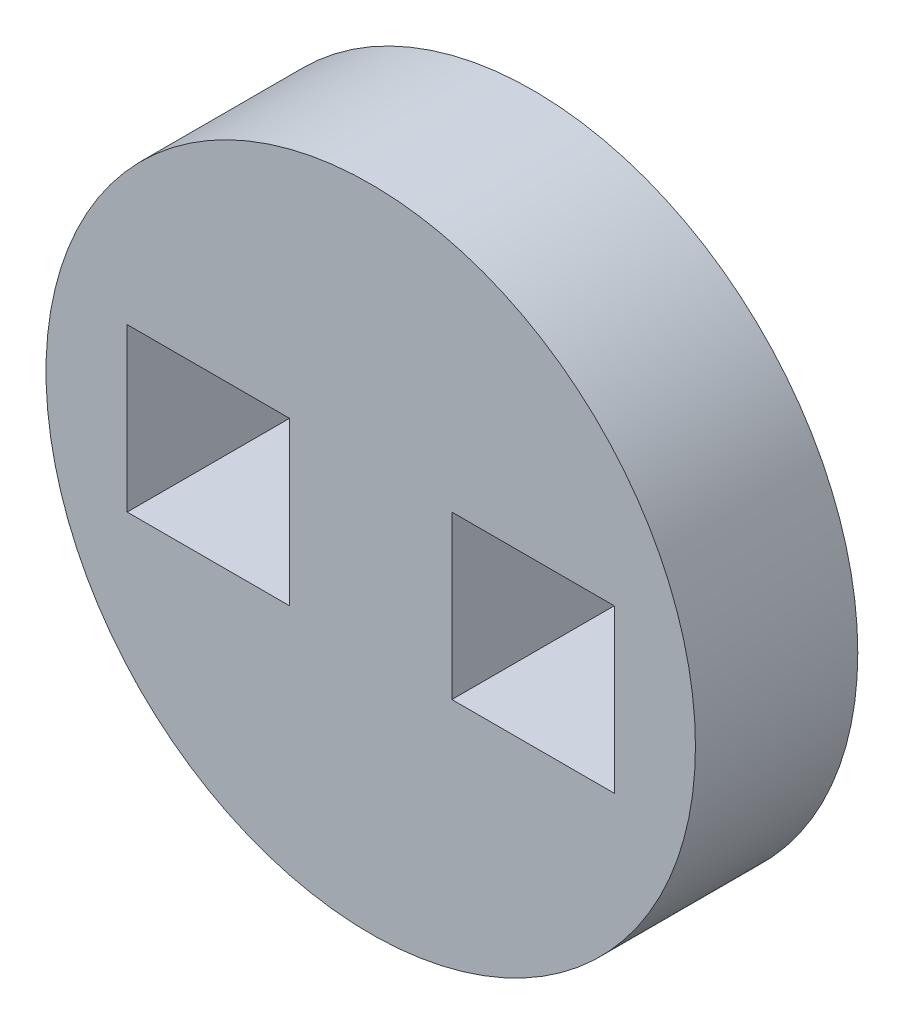
SolidWorks part; units mm, degrees
ref_plane "Front Plane" through (0, 0, 0) normal (0, 0, 1) x (1, 0, 0)
ref_plane "Top Plane" through (0, 0, 0) normal (0, 1, 0) x (1, 0, 0)
ref_plane "Right Plane" through (0, 0, 0) normal (1, 0, 0) x (0, 0, -1)
sketch "Sketch1" plane through (0, 0, 0) normal (0, 0, 1) x (1, 0, 0)
  line L1 (1.5875, -1.5875) -> (4.7625, -1.5875)
  line L2 (1.5875, -1.5875) -> (1.5875, 1.5875)
  line L3 (1.5875, 1.5875) -> (4.7625, 1.5875)
  line L4 (4.7625, -1.5875) -> (4.7625, 1.5875)
  line L5 (1.5875, -1.5875) -> (4.7625, 1.5875) construction
  line L6 (1.5875, 1.5875) -> (4.7625, -1.5875) construction
  line L7 (-4.7625, -1.5875) -> (-1.5875, -1.5875)
  line L8 (-4.7625, -1.5875) -> (-4.7625, 1.5875)
  line L9 (-4.7625, 1.5875) -> (-1.5875, 1.5875)
  line L10 (-1.5875, -1.5875) -> (-1.5875, 1.5875)
  line L11 (-4.7625, -1.5875) -> (-1.5875, 1.5875) construction
  line L12 (-4.7625, 1.5875) -> (-1.5875, -1.5875) construction
  circle A0 centre (0, 0) radius 6.35
  point P3 (3.175, 0)
  point P8 (-3.175, 0)
  point P13 (0, 0)
  dimension "D1" = 12.7
  dimension "D2" = 3.175
  dimension "D3" = 3.175
  dimension "D4" = 3.175
extrude "Boss-Extrude1" add sketch "Sketch1" along normal blind 3.175
